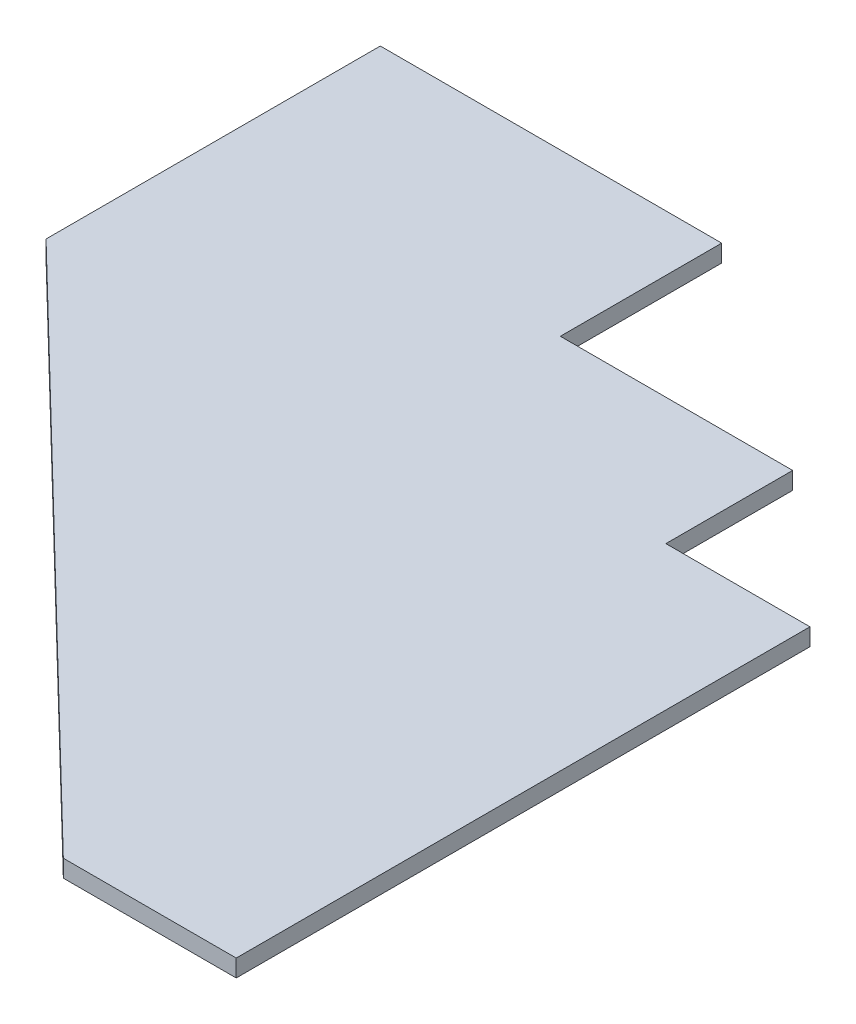
SolidWorks part; units mm, degrees
material "AISI 1020"
ref_plane "Спереди" through (0, 0, 0) normal (0, 0, 1) x (1, 0, 0)
ref_plane "Сверху" through (0, 0, 0) normal (0, 1, 0) x (1, 0, 0)
ref_plane "Справа" through (0, 0, 0) normal (1, 0, 0) x (0, 0, -1)
sketch "Эскиз1" plane through (0, 0, 0) normal (0, 1, 0) x (1, 0, 0)
  line L0 (0, 44) -> (0, 0)
  line L1 (0, 0) -> (50, 0)
  line L2 (50, 0) -> (50, -199.1112)
  line L3 (50, -199.1112) -> (-10, -199.1112)
  line L4 (-10, -199.1112) -> (-199.1112, -16)
  line L5 (-199.1112, -16) -> (-199.1112, 44)
  line L6 (-199.1112, 44) -> (0, 44) construction
  line L7 (94, 0) -> (6, 0) construction
  line L8 (0, 6) -> (0, 94) construction
  line L9 (50, 148.4) -> (50, 51.6) construction
  line L11 (-4.2376, 44) -> (-2358.6111, 44) construction
  line L12 (-80.6264, 44) -> (-80.6264, 100)
  line L13 (-80.6264, 100) -> (-199.1112, 100)
  line L14 (-199.1112, 100) -> (-199.1112, 44)
  line L15 (100, 100) -> (-5050, 100) construction
  line L16 (-70.6264, 47) -> (-70.6264, 91) construction
  line L17 (-80.6264, 44) -> (0, 44)
  point P23 (-80.6264, 72)
  dimension "D1" = 10
  dimension "D2" = 150
  dimension "D3" = 10
base flange "Базовая кромка1" sketch "Эскиз1" thickness 6 reverse thickness direction no parameters "D1"=0.75
sketch "Сгиб-Линии1" plane through (0, 0, 0) normal (0, 1, 0) x (1, 0, 0)
sketch "Граничная рамка1" plane through (0, 0, 0) normal (0, 1, 0) x (1, 0, 0)
sheet metal parameters "Листовой металл3" thickness 6 parameters "D1"=0.75
flat pattern "Развертка3" [suppressed]
sketch "Сгиб-Линии2" plane through (0, 0, 0) normal (0, 1, 0) x (1, 0, 0)
sketch "Граничная рамка2" [suppressed] plane through (0, 0, 0) normal (0, 1, 0) x (1, 0, 0)
